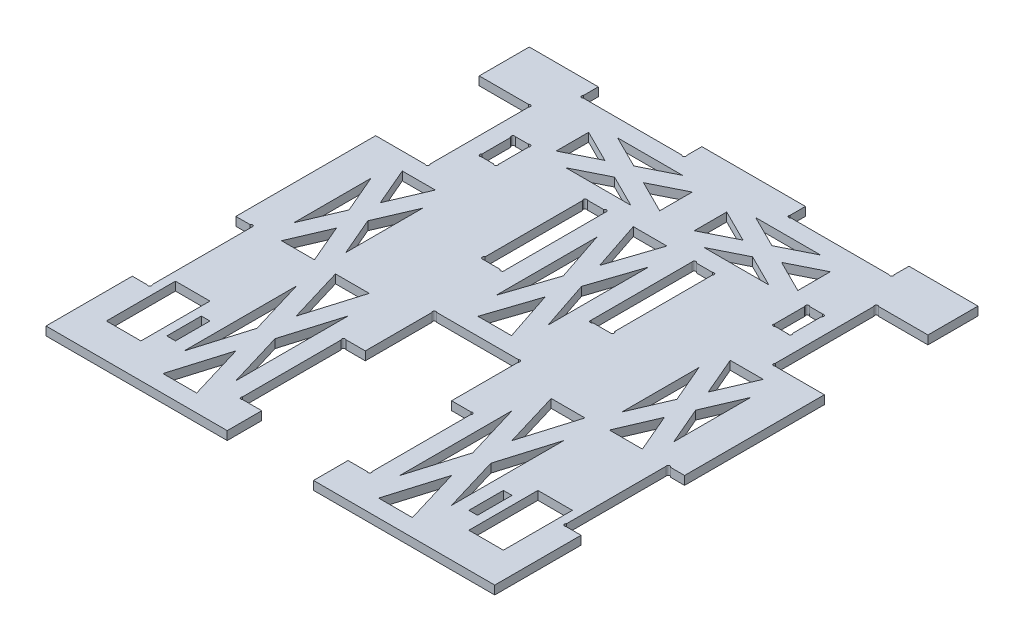
SolidWorks part; units mm, degrees
material "7050-T73510"
ref_plane "Front Plane" through (0, 0, 0) normal (0, 0, 1) x (1, 0, 0)
ref_plane "Top Plane" through (0, 0, 0) normal (0, 1, 0) x (1, 0, 0)
ref_plane "Right Plane" through (0, 0, 0) normal (1, 0, 0) x (0, 0, -1)
sketch "Sketch1" plane through (0, 0, 0) normal (0, 1, 0) x (1, 0, 0)
  line L1 (-165.1, -177.8) -> (165.1, -177.8)
  line L2 (-165.1, -177.8) -> (-165.1, 177.8)
  line L3 (-165.1, 177.8) -> (165.1, 177.8)
  line L4 (165.1, -177.8) -> (165.1, 177.8)
  line L5 (-165.1, -177.8) -> (165.1, 177.8) construction
  line L6 (-165.1, 177.8) -> (165.1, -177.8) construction
  point P0 (0, 0)
  dimension "D1" = 355.6
  dimension "D2" = 330.2
extrude "Boss-Extrude1" add sketch "Sketch1" along normal blind 6.35
sketch "Sketch2" plane through (0, 6.35, 0) normal (0, 1, 0) x (1, 0, 0)
  line L0 (-165.1, -177.8) -> (165.1, -177.8) construction
  line L1 (-31.75, -25.4) -> (31.75, -25.4)
  line L2 (-31.75, -25.4) -> (-31.75, -177.8)
  line L3 (-31.75, -177.8) -> (31.75, -177.8)
  line L4 (31.75, -25.4) -> (31.75, -177.8)
  line L5 (-31.75, -25.4) -> (31.75, -177.8) construction
  line L6 (-31.75, -177.8) -> (31.75, -25.4) construction
  point P0 (0, -101.6)
  dimension "D1" = 152.4
  dimension "D2" = 63.5
extrude "Cut-Extrude1" cut sketch "Sketch2" against normal through all
sketch "Sketch3" plane through (0, 6.35, 0) normal (0, 1, 0) x (1, 0, 0)
  line L0 (165.1, -177.8) -> (165.1, 177.8) construction
  line L5 (152.4, 140.97) -> (127, 140.97)
  line L11 (152.4, 140.97) -> (152.4, 64.77)
  line L13 (152.4, 64.77) -> (127, 64.77)
  line L15 (127, 140.97) -> (127, 64.77)
  line L16 (165.1, 177.8) -> (-165.1, 177.8) construction
  line L17 (114.3, 90.17) -> (101.6, 90.17)
  line L18 (114.3, 90.17) -> (114.3, 115.57)
  line L19 (114.3, 115.57) -> (101.6, 115.57)
  line L20 (101.6, 90.17) -> (101.6, 115.57)
  line L21 (0, -3.4925) -> (0, 3.4925) construction
  line L22 (-101.6, 90.17) -> (-101.6, 115.57)
  line L23 (-114.3, 115.57) -> (-101.6, 115.57)
  line L24 (-114.3, 90.17) -> (-114.3, 115.57)
  line L25 (-114.3, 90.17) -> (-101.6, 90.17)
  line L26 (-127, 140.97) -> (-127, 64.77)
  line L27 (-152.4, 64.77) -> (-127, 64.77)
  line L28 (-152.4, 140.97) -> (-152.4, 64.77)
  line L29 (-152.4, 140.97) -> (-127, 140.97)
  point P14 (114.3, 102.87)
  point P15 (127, 102.87)
  dimension "D1" = 25.4
  dimension "D2" = 12.7
  dimension "D3" = 12.7
  dimension "D4" = 12.7
  dimension "D5" = 25.4
  dimension "D6" = 76.2
  dimension "D7" = 36.83
extrude "Cut-Extrude2" cut sketch "Sketch3" against normal through all contours L5 L15 L13 L11 | L20 L17 L18 L19 | L29 L28 L27 L26 | L24 L25 L22 L23 | L26 L27 L28 L29 region at (139.7, 6.35, -102.87) region at (107.95, 6.35, -102.87) region at (-107.95, 6.35, -102.87) region at (-139.7, 6.35, -102.87)
sketch "Sketch4" plane through (0, 6.35, 0) normal (0, 1, 0) x (1, 0, 0)
  line L0 (-165.1, 177.8) -> (-165.1, -177.8) construction
  line L1 (-165.1, 140.97) -> (-152.4, 140.97)
  line L2 (-165.1, 140.97) -> (-165.1, 64.77)
  line L3 (-165.1, 64.77) -> (-152.4, 64.77)
  line L4 (-152.4, 140.97) -> (-152.4, 64.77)
  line L5 (0, -3.4925) -> (0, 3.4925) construction
  line L6 (-165.1, -114.3) -> (-152.4, -114.3)
  line L7 (-165.1, -114.3) -> (-165.1, -38.1)
  line L8 (-165.1, -38.1) -> (-152.4, -38.1)
  line L9 (-152.4, -114.3) -> (-152.4, -38.1)
  line L10 (165.1, 64.77) -> (152.4, 64.77)
  line L11 (152.4, 140.97) -> (152.4, 64.77)
  line L12 (165.1, 140.97) -> (152.4, 140.97)
  line L13 (165.1, 140.97) -> (165.1, 64.77)
  line L14 (165.1, -38.1) -> (152.4, -38.1)
  line L15 (152.4, -114.3) -> (152.4, -38.1)
  line L16 (165.1, -114.3) -> (152.4, -114.3)
  line L17 (165.1, -114.3) -> (165.1, -38.1)
  line L18 (165.1, 177.8) -> (-165.1, 177.8) construction
  line L19 (114.3, 165.1) -> (38.1, 165.1)
  line L20 (-114.3, 177.8) -> (-38.1, 177.8)
  line L21 (-114.3, 177.8) -> (-114.3, 165.1)
  line L22 (-114.3, 165.1) -> (-38.1, 165.1)
  line L23 (-38.1, 177.8) -> (-38.1, 165.1)
  line L24 (38.1, 177.8) -> (38.1, 165.1)
  line L25 (114.3, 177.8) -> (38.1, 177.8)
  line L26 (114.3, 177.8) -> (114.3, 165.1)
  line L27 (-31.75, -25.4) -> (-31.75, -177.8) construction
  line L28 (-31.75, -152.4) -> (-47.625, -152.4)
  line L29 (-31.75, -152.4) -> (-31.75, -76.2)
  line L30 (-31.75, -76.2) -> (-47.625, -76.2)
  line L31 (-47.625, -152.4) -> (-47.625, -76.2)
  line L32 (-165.1, -177.8) -> (-31.75, -177.8) construction
  line L33 (31.75, 101.6) -> (47.625, 101.6)
  line L34 (-31.75, 25.4) -> (-47.625, 25.4)
  line L35 (-31.75, 25.4) -> (-31.75, 101.6)
  line L36 (-31.75, 101.6) -> (-47.625, 101.6)
  line L37 (-47.625, 25.4) -> (-47.625, 101.6)
  line L38 (47.625, 25.4) -> (47.625, 101.6)
  line L39 (31.75, 25.4) -> (47.625, 25.4)
  line L40 (31.75, 25.4) -> (31.75, 101.6)
  line L41 (31.75, -76.2) -> (47.625, -76.2)
  line L42 (47.625, -152.4) -> (47.625, -76.2)
  line L43 (31.75, -152.4) -> (47.625, -152.4)
  line L44 (31.75, -152.4) -> (31.75, -76.2)
  dimension "D1" = 12.7
  dimension "D2" = 12.7
  dimension "D3" = 76.2
  dimension "D4" = 76.2
  dimension "D5" = 36.83
  dimension "D6" = 215.9
  dimension "D7" = 12.7
  dimension "D8" = 76.2
  dimension "D9" = 76.2
  dimension "D10" = 15.875
  dimension "D11" = 76.2
  dimension "D12" = 25.4
  dimension "D13" = 76.2
  dimension "D14" = 15.875
  dimension "D15" = 203.2
  dimension "D16" = 63.5
extrude "Cut-Extrude3" cut sketch "Sketch4" against normal through all
sketch "Sketch5" plane through (0, 6.35, 0) normal (0, 1, 0) x (1, 0, 0)
  line L0 (-165.1, -177.8) -> (-31.75, -177.8) construction
  line L1 (-98.425, -165.1) -> (-60.325, -165.1)
  line L2 (-98.425, -165.1) -> (-98.425, -38.1)
  line L3 (-98.425, -38.1) -> (-60.325, -38.1)
  line L4 (-60.325, -165.1) -> (-60.325, -38.1)
  line L5 (-98.425, -165.1) -> (-60.325, -38.1) construction
  line L6 (-98.425, -38.1) -> (-60.325, -165.1) construction
  line L7 (-139.7, -36.83) -> (-101.6, -36.83)
  line L8 (-139.7, -36.83) -> (-139.7, 52.07)
  line L9 (-139.7, 52.07) -> (-101.6, 52.07)
  line L10 (-101.6, -36.83) -> (-101.6, 52.07)
  line L11 (-139.7, -36.83) -> (-101.6, 52.07) construction
  line L12 (-139.7, 52.07) -> (-101.6, -36.83) construction
  line L13 (-88.9, 114.3) -> (-12.7, 114.3)
  line L14 (-88.9, 114.3) -> (-88.9, 152.4)
  line L15 (-88.9, 152.4) -> (-12.7, 152.4)
  line L16 (-12.7, 114.3) -> (-12.7, 152.4)
  line L17 (-88.9, 114.3) -> (-12.7, 152.4) construction
  line L18 (-88.9, 152.4) -> (-12.7, 114.3) construction
  line L23 (0, -3.4925) -> (0, 3.4925) construction
  line L24 (-19.05, -12.7) -> (19.05, -12.7)
  line L25 (-152.4, -114.3) -> (-152.4, -38.1) construction
  line L26 (-152.4, -38.1) -> (-165.1, -38.1) construction
  line L27 (-47.625, -76.2) -> (-47.625, -152.4) construction
  line L28 (-165.1, 64.77) -> (-165.1, -38.1) construction
  line L29 (-165.1, 64.77) -> (-127, 64.77) construction
  line L31 (-19.05, -12.7) -> (-19.05, 101.6)
  line L32 (-19.05, 101.6) -> (19.05, 101.6)
  line L33 (19.05, -12.7) -> (19.05, 101.6)
  line L34 (-19.05, -12.7) -> (19.05, 101.6) construction
  line L35 (-19.05, 101.6) -> (19.05, -12.7) construction
  line L36 (31.75, -25.4) -> (-31.75, -25.4) construction
  line L37 (-31.75, 25.4) -> (-31.75, 101.6) construction
  line L38 (-31.75, 101.6) -> (-47.625, 101.6) construction
  line L39 (-101.6, 90.17) -> (-101.6, 115.57) construction
  line L40 (-114.3, 165.1) -> (-38.1, 165.1) construction
  line L41 (-104.5072, -39.9247) -> (-66.4072, -166.9247)
  line L42 (-92.3428, -166.9247) -> (-54.2428, -39.9247)
  line L43 (-145.5366, 49.5686) -> (-107.4366, -39.3314)
  line L44 (-133.8634, -39.3314) -> (-95.7634, 49.5686)
  line L45 (-25.0741, 99.592) -> (13.0259, -14.708)
  line L46 (-13.0259, -14.708) -> (25.0741, 99.592)
  line L47 (-91.7398, 146.7204) -> (-15.5398, 108.6204)
  line L48 (-86.0602, 108.6204) -> (-9.8602, 146.7204)
  line L49 (-92.3428, -36.2753) -> (-54.2428, -163.2753)
  line L50 (-104.5072, -163.2753) -> (-66.4072, -36.2753)
  line L51 (-133.8634, 54.5714) -> (-95.7634, -34.3286)
  line L52 (-145.5366, -34.3286) -> (-107.4366, 54.5714)
  line L53 (-13.0259, 103.608) -> (25.0741, -10.692)
  line L54 (-25.0741, -10.692) -> (13.0259, 103.608)
  line L55 (-86.0602, 158.0796) -> (-9.8602, 119.9796)
  line L56 (-91.7398, 119.9796) -> (-15.5398, 158.0796)
  line L57 (-146.05, -101.6) -> (-120.65, -101.6)
  line L58 (-146.05, -101.6) -> (-146.05, -152.4)
  line L59 (-146.05, -152.4) -> (-120.65, -152.4)
  line L60 (-120.65, -101.6) -> (-120.65, -152.4)
  line L63 (-114.3, -139.7) -> (-107.95, -139.7)
  line L64 (-114.3, -139.7) -> (-114.3, -114.3)
  line L65 (-114.3, -114.3) -> (-107.95, -114.3)
  line L66 (-107.95, -139.7) -> (-107.95, -114.3)
  line L67 (-114.3, -139.7) -> (-107.95, -114.3) construction
  line L68 (-114.3, -114.3) -> (-107.95, -139.7) construction
  point P0 (-79.375, -101.6)
  point P5 (-120.65, 7.62)
  point P10 (-50.8, 133.35)
  point P15 (0, 44.45)
  point P27 (-158.75, -38.1)
  point P34 (-111.125, -127)
  point P45 (-39.6875, 101.6)
  point P87 (-120.65, -127)
  dimension "D1" = 12.7
  dimension "D2" = 38.1
  dimension "D3" = 0
  dimension "D4" = 12.7
  dimension "D5" = 88.9
  dimension "D6" = 25.4
  dimension "D7" = 12.7
  dimension "D8" = 38.1
  dimension "D9" = 12.7
  dimension "D10" = 12.7
  dimension "D11" = 12.7
  dimension "D12" = 12.7
  dimension "D13" = 12.7
  dimension "D14" = 12.7
  dimension "D17" = 25.4
  dimension "D18" = 50.8
  dimension "D19" = 12.7
  dimension "D20" = 6.35
  dimension "D21" = 6.35
  dimension "D22" = 38.1
  dimension "D23" = 25.4
  dimension "D15" = 6.35
  dimension "D16" = 6.35
extrude "Cut-Extrude4" cut sketch "Sketch5" against normal through all contours L42 L1 L41 | L2 L50 L41 | L49 L50 L3 | L42 L49 L4 | L44 L7 L43 | L8 L52 L43 | L51 L52 L9 | L44 L51 L10 | L46 L53 L33 | L53 L54 L32 | L31 L54 L45 | L46 L24 L45 | L48 L13 L47 | L48 L55 L16 | L55 L56 L15 | L14 L56 L47 | L60 L57 L58 L59 | L63 L66 L65 L64 region at (-79.375, 6.35, 151.2995) region at (-94.2849, 6.35, 101.6) region at (-64.4651, 6.35, 101.6) region at (-79.375, 6.35, 51.9005) region at (-120.65, 6.35, 27.3867) region at (-135.6529, 6.35, -7.62) region at (-105.6471, 6.35, -7.62) region at (-120.65, 6.35, -42.6267) region at (-50.8, 6.35, -118.2835) region at (-80.933, 6.35, -133.35) region at (-20.667, 6.35, -133.35) region at (-50.8, 6.35, -148.4165) region at (0, 6.35, 0.3435) region at (-14.9312, 6.35, -44.45) region at (14.9312, 6.35, -44.45) region at (0, 6.35, -89.2435) region at (-133.35, 6.35, 127) region at (-111.125, 6.35, 127)
mirror "Mirror1" about plane through (0, 0, 0) normal (1, 0, 0) of "Cut-Extrude4"
sketch "Sketch6" plane through (0, 6.35, 0) normal (0, 1, 0) x (1, 0, 0)
  circle A0 centre (-127.8194, 65.7403) radius 1.27
  circle A1 centre (-127.9383, 140.1141) radius 1.27
  circle A2 centre (-113.3907, 165.9867) radius 1.27
  circle A3 centre (-39.124, 165.8512) radius 1.27
  circle A4 centre (-46.8424, 100.5998) radius 1.27
  circle A5 centre (-32.9403, 101.1573) radius 1.27
  circle A7 centre (-47.2982, 26.6272) radius 1.27
  circle A8 centre (-32.9079, 25.9216) radius 1.27
  circle A9 centre (-153.5668, -38.6014) radius 1.27
  circle A10 centre (-153.1517, -113.2764) radius 1.27
  circle A11 centre (-46.7669, -151.4637) radius 1.27
  circle A12 centre (-46.8208, -77.1829) radius 1.27
  circle A13 centre (-30.886, -26.3308) radius 1.27
  circle A14 centre (-113.678, 114.4628) radius 1.27
  circle A15 centre (-102.5148, 114.6891) radius 1.27
  circle A17 centre (-102.6381, 90.9016) radius 1.27
  circle A18 centre (-113.5656, 91.2061) radius 1.27
extrude "Cut-Extrude5" cut sketch "Sketch6" against normal through all
mirror "Mirror2" about plane through (0, 0, 0) normal (1, 0, 0) of "Cut-Extrude5"
